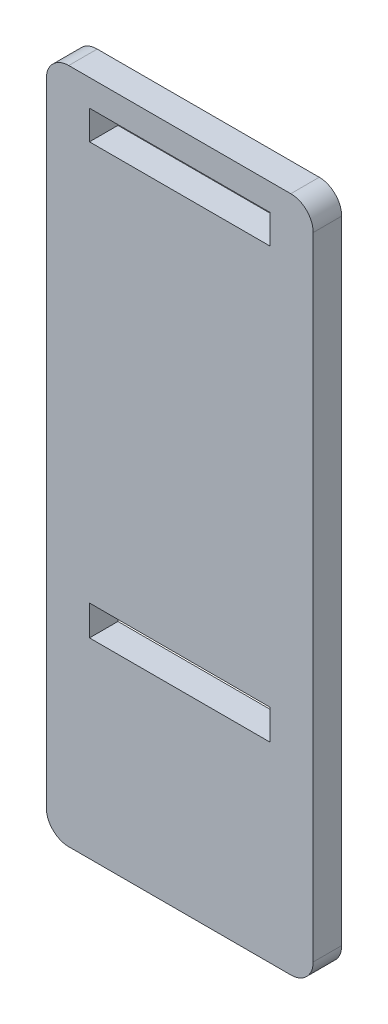
SolidWorks part; units mm, degrees
material "AISI 1020"
ref_plane "Plano frontal" through (0, 0, 0) normal (0, 0, 1) x (1, 0, 0)
ref_plane "Plano superior" through (0, 0, 0) normal (0, 1, 0) x (1, 0, 0)
ref_plane "Plano direito" through (0, 0, 0) normal (1, 0, 0) x (0, 0, -1)
sketch "Esboço1" plane through (0, 0, 0) normal (0, 0, 1) x (1, 0, 0)
  line L0 (0, 150.825) -> (0, 132.475) construction
  line L1 (-49.5, -150.825) -> (49.5, -150.825)
  line L2 (-59.5, -140.825) -> (-59.5, 140.825)
  line L3 (-49.5, 150.825) -> (49.5, 150.825)
  line L4 (59.5, -140.825) -> (59.5, 140.825)
  line L5 (-59.5, -150.825) -> (59.5, 150.825) construction
  line L6 (-59.5, 150.825) -> (59.5, -150.825) construction
  line L7 (0, 132.475) -> (0, -58.825) construction
  line L13 (40.25, 138.975) -> (-40.25, 138.975)
  line L14 (40.25, 138.975) -> (40.25, 125.975)
  line L19 (40.25, 125.975) -> (-40.25, 125.975)
  line L20 (-40.25, 138.975) -> (-40.25, 125.975)
  line L21 (40.25, 138.975) -> (-40.25, 125.975) construction
  line L22 (40.25, 125.975) -> (-40.25, 138.975) construction
  line L23 (40.25, -52.0838) -> (-40.25, -52.0838)
  line L24 (40.25, -52.0838) -> (40.25, -65.5662)
  line L25 (40.25, -65.5662) -> (-40.25, -65.5662)
  line L26 (-40.25, -52.0838) -> (-40.25, -65.5662)
  line L27 (40.25, -52.0838) -> (-40.25, -65.5662) construction
  line L28 (40.25, -65.5662) -> (-40.25, -52.0838) construction
  arc A0 (49.5, -150.825) -> (59.5, -140.825) centre (49.5, -140.825) ccw
  arc A1 (-49.5, -150.825) -> (-59.5, -140.825) centre (-49.5, -140.825) cw
  arc A2 (-59.5, 140.825) -> (-49.5, 150.825) centre (-49.5, 140.825) cw
  arc A3 (49.5, 150.825) -> (59.5, 140.825) centre (49.5, 140.825) cw
  point P0 (0, 0)
  dimension "D3" = 10
  dimension "D1" = 301.65
  dimension "D2" = 119
  dimension "D4" = 80.5
  dimension "D5" = 13
  dimension "D6" = 18.35
  dimension "D7" = 191.3
base flange "Flange-base1" sketch "Esboço1" thickness 12.7 reverse thickness direction no parameters "D1"=0.7366
sketch "Curva-Linhas1" [suppressed] plane through (0, 0, 0) normal (0, 1, 0) x (1, 0, 0)
sketch "Caixa delimitadora1" [suppressed] plane through (0, 0, 0) normal (0, 1, 0) x (1, 0, 0)
sheet metal parameters "Chapa metálica1" thickness 12.7 parameters "D1"=0.7366
flat pattern "Padrão-Plano1" [suppressed]
sketch "Curva-Linhas2" plane through (0, 0, 0) normal (0, 1, 0) x (1, 0, 0)
sketch3d "Caixa delimitadora2" [suppressed]
  line L0 (-10, -10, 0) -> (-10, 291.65, 0) construction
  line L1 (109, -10, 0) -> (109, 291.65, 0) construction
  line L2 (-10, -10, 0) -> (109, -10, 0) construction
  line L3 (-10, 291.65, 0) -> (109, 291.65, 0) construction
